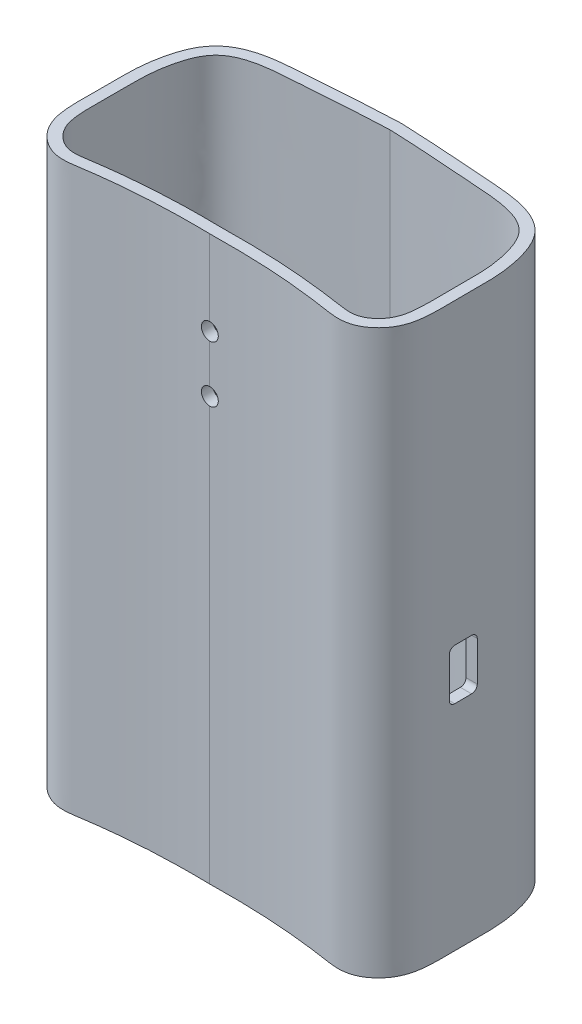
SolidWorks part; units mm, degrees
ref_plane "Ön Düzlem" through (0, 0, 0) normal (0, 0, 1) x (1, 0, 0)
ref_plane "Üst Düzlem" through (0, 0, 0) normal (0, 1, 0) x (1, 0, 0)
ref_plane "Sağ Düzlem" through (0, 0, 0) normal (1, 0, 0) x (0, 0, -1)
sketch "Çizim1" plane through (0, 0, 0) normal (0, 1, 0) x (1, 0, 0)
  line L0 (0, 17.9288) -> (0, -12.0712) construction
  line L1 (0, 0) -> (-30, 0) construction
  line L2 (-108.3091, -42.1463) -> (-63.9653, -42.1463) construction
  spline S0 degree 3 poles (0, 17.9288) (-5.8202, 17.7095) (-13.9034, 17.0426) (-26.8757, 16.196) (-29.5503, 8.9293) (-30.0905, 4.3361) (-29.9407, -0.8874) (-30.1549, -5.7017) (-29.6372, -10.9288) (-26.0312, -14.0818) (-15.7201, -12.3493) (-7.8072, -11.9389) (0, -12.0712) knots 0 0 0 0 0.19846 0.336013 0.394477 0.45973 0.505377 0.582751 0.635933 0.690009 0.731881 1 1 1 1
  spline S1 degree 3 poles (0, 17.9288) (5.8202, 17.7095) (13.9034, 17.0426) (26.8757, 16.196) (29.5503, 8.9293) (30.0905, 4.3361) (29.9407, -0.8874) (30.1549, -5.7017) (29.6372, -10.9288) (26.0312, -14.0818) (15.7201, -12.3493) (7.8072, -11.9389) (0, -12.0712) knots 0 0 0 0 0.19846 0.336013 0.394477 0.45973 0.505377 0.582751 0.635933 0.690009 0.731881 1 1 1 1
  spline S2 degree 1 poles (0, 19.9303) (0, -14.0714) knots 0 0 1 1 construction
  spline S3 degree 1 poles (0, 19.9303) (0, -14.0714) knots 0 0 1 1 construction
  spline S4 degree 3 poles (0, 19.9303) (-0.4569, 19.913) (-1.3788, 19.8761) (-3.1568, 19.7944) (-5.3169, 19.678) (-7.8418, 19.5195) (-11.19, 19.2895) (-14.5919, 19.03) (-18.2872, 18.7842) (-21.2619, 18.4861) (-24.2247, 17.8563) (-26.5803, 16.8232) (-28.2551, 15.5188) (-29.6889, 13.8306) (-30.7777, 11.4296) (-31.5143, 8.5883) (-31.9232, 5.825) (-32.0441, 3.0566) (-31.9879, 0.4286) (-32.0171, -2.0683) (-32.052, -4.7106) (-32.0036, -7.4061) (-31.6486, -10.0115) (-30.6275, -12.1561) (-29.5067, -13.557) (-28.1065, -14.6986) (-26.705, -15.3667) (-25.4582, -15.6359) (-24.2895, -15.7185) (-22.9553, -15.6032) (-21.6185, -15.3841) (-20.348, -15.2005) (-19.0747, -15.0274) (-17.3942, -14.8187) (-15.3102, -14.5944) (-12.8229, -14.3819) (-9.5026, -14.1699) (-6.1385, -14.0592) (-2.6849, -14.0381) (-0.8891, -14.0564) (0, -14.0714) knots -0.000856 -0.000856 -0.000856 -0.000856 0.014788 0.030433 0.061722 0.093011 0.1243 0.186877 0.218166 0.249455 0.280744 0.312033 0.327677 0.343322 0.37461 0.405899 0.437188 0.468477 0.499766 0.531055 0.562344 0.593633 0.624921 0.640566 0.65621 0.671855 0.687499 0.695321 0.703144 0.718788 0.734432 0.750077 0.765721 0.781366 0.812655 0.843944 0.875232 0.93781 0.969099 1.000388 1.000388 1.000388 1.000388
  spline S5 degree 3 poles (0, -14.0714) (0.8891, -14.0564) (2.6849, -14.0381) (6.1385, -14.0592) (9.5026, -14.1699) (12.8229, -14.3819) (15.3102, -14.5944) (17.3942, -14.8187) (19.0747, -15.0274) (20.348, -15.2005) (21.6185, -15.3841) (22.9553, -15.6032) (24.2895, -15.7185) (25.4582, -15.6359) (26.705, -15.3667) (28.1065, -14.6986) (29.5067, -13.557) (30.6275, -12.1561) (31.6486, -10.0115) (32.0036, -7.4061) (32.052, -4.7106) (32.0171, -2.0683) (31.9879, 0.4286) (32.0441, 3.0566) (31.9232, 5.825) (31.5143, 8.5883) (30.7777, 11.4296) (29.6889, 13.8306) (28.2551, 15.5188) (26.5803, 16.8232) (24.2247, 17.8563) (21.2619, 18.4861) (18.2872, 18.7842) (14.5919, 19.03) (11.19, 19.2895) (7.8418, 19.5195) (5.3169, 19.678) (3.1568, 19.7944) (1.3788, 19.8761) (0.4569, 19.913) (0, 19.9303) knots -0.000856 -0.000856 -0.000856 -0.000856 0.030433 0.061722 0.1243 0.155588 0.186877 0.218166 0.233811 0.249455 0.265099 0.280744 0.296388 0.304211 0.312033 0.327677 0.343322 0.358966 0.37461 0.405899 0.437188 0.468477 0.499766 0.531055 0.562344 0.593633 0.624921 0.65621 0.671855 0.687499 0.718788 0.750077 0.781366 0.812655 0.875232 0.906521 0.93781 0.969099 0.984743 1.000388 1.000388 1.000388 1.000388
  dimension "D1" = 30
  dimension "D2" = 30
  dimension "D3" = 2
extrude "Yükseklik-Ekstrüzyon1" add sketch "Çizim1" along normal blind 100
sketch "Çizim2" plane through (0, 100, 0) normal (0, 1, 0) x (1, 0, 0)
  line L0 (0, -14.0714) -> (0, -12.0712)
ref_plane "Düzlem1" through (0, 0, 14.0714) normal (0, 0, -1) x (-1, 0, 0)
sketch "Çizim3" plane through (0, 0, 14.0714) normal (0, 0, -1) x (-1, 0, 0)
  line L0 (0, 100) -> (0, 0) construction
  circle A0 centre (0, 85) radius 1.5
  circle A1 centre (0, 75) radius 1.5
  dimension "D1" = 10
  dimension "D3" = 3
  dimension "D2" = 15
extrude "Kes-Ekstrüzyon1" cut sketch "Çizim3" along normal blind 10
sketch "Çizim4" plane through (0, 0, 0) normal (0, -1, 0) x (1, 0, 0)
  spline S5 degree 3 poles (3998.4121, 83.4226) (-102.3546, -17.7812) (-29.2856, -21.2861) (3.1568, -19.7944) (5.3169, -19.678) (7.8418, -19.5195) (11.19, -19.2895) (14.5919, -19.03) (18.2872, -18.7842) (21.2619, -18.4861) (24.2247, -17.8563) (26.5803, -16.8232) (28.2551, -15.5188) (29.6889, -13.8306) (30.7777, -11.4296) (31.5143, -8.5883) (31.9232, -5.825) (32.0441, -3.0566) (31.9879, -0.4286) (32.0171, 2.0683) (32.052, 4.7106) (32.0036, 7.4061) (31.6486, 10.0115) (30.6275, 12.1561) (29.5067, 13.557) (28.1065, 14.6986) (26.705, 15.3667) (25.4582, 15.6359) (24.2895, 15.7185) (22.9553, 15.6032) (21.6185, 15.3841) (20.348, 15.2005) (19.0747, 15.0274) (17.3942, 14.8187) (15.3102, 14.5944) (12.8229, 14.3819) (9.5026, 14.1699) (6.1385, 14.0592) (-43.8501, 13.7536) (-145.9249, 35.9842) (3997.0667, -133.1935) knots -1.08014 -1.08014 -1.08014 -1.08014 0.014788 0.030433 0.061722 0.093011 0.1243 0.186877 0.218166 0.249455 0.280744 0.312033 0.327677 0.343322 0.37461 0.405899 0.437188 0.468477 0.499766 0.531055 0.562344 0.593633 0.624921 0.640566 0.65621 0.671855 0.687499 0.695321 0.703144 0.718788 0.734432 0.750077 0.765721 0.781366 0.812655 0.843944 0.875232 0.93781 0.969099 2.686743 2.686743 2.686743 2.686743 only from (0, -19.9303) to (0, 14.0714)
  spline S6 degree 3 poles (-3996.9772, -133.1899) (145.9234, 35.9838) (43.8498, 13.7536) (-6.1385, 14.0592) (-9.5026, 14.1699) (-12.8229, 14.3819) (-15.3102, 14.5944) (-17.3942, 14.8187) (-19.0747, 15.0274) (-20.348, 15.2005) (-21.6185, 15.3841) (-22.9553, 15.6032) (-24.2895, 15.7185) (-25.4582, 15.6359) (-26.705, 15.3667) (-28.1065, 14.6986) (-29.5067, 13.557) (-30.6275, 12.1561) (-31.6486, 10.0115) (-32.0036, 7.4061) (-32.052, 4.7106) (-32.0171, 2.0683) (-31.9879, -0.4286) (-32.0441, -3.0566) (-31.9232, -5.825) (-31.5143, -8.5883) (-30.7777, -11.4296) (-29.6889, -13.8306) (-28.2551, -15.5188) (-26.5803, -16.8232) (-24.2247, -17.8563) (-21.2619, -18.4861) (-18.2872, -18.7842) (-14.5919, -19.03) (-11.19, -19.2895) (-7.8418, -19.5195) (-5.3169, -19.678) (-3.1568, -19.7944) (29.2854, -21.2861) (102.3539, -17.7813) (-3998.3551, 83.4212) knots -1.687199 -1.687199 -1.687199 -1.687199 0.030433 0.061722 0.1243 0.155588 0.186877 0.218166 0.233811 0.249455 0.265099 0.280744 0.296388 0.304211 0.312033 0.327677 0.343322 0.358966 0.37461 0.405899 0.437188 0.468477 0.499766 0.531055 0.562344 0.593633 0.624921 0.65621 0.671855 0.687499 0.718788 0.750077 0.781366 0.812655 0.875232 0.906521 0.93781 0.969099 0.984743 2.079666 2.079666 2.079666 2.079666 only from (0, 14.0714) to (0, -19.9303)
  spline S7 degree 3 poles (0, -19.9303) (0.4569, -19.913) (1.3788, -19.8761) (3.1568, -19.7944) (5.3169, -19.678) (7.8418, -19.5195) (11.19, -19.2895) (14.5919, -19.03) (18.2872, -18.7842) (21.2619, -18.4861) (24.2247, -17.8563) (26.5803, -16.8232) (28.2551, -15.5188) (29.6889, -13.8306) (30.7777, -11.4296) (31.5143, -8.5883) (31.9232, -5.825) (32.0441, -3.0566) (31.9879, -0.4286) (32.0171, 2.0683) (32.052, 4.7106) (32.0036, 7.4061) (31.6486, 10.0115) (30.6275, 12.1561) (29.5067, 13.557) (28.1065, 14.6986) (26.705, 15.3667) (25.4582, 15.6359) (24.2895, 15.7185) (22.9553, 15.6032) (21.6185, 15.3841) (20.348, 15.2005) (19.0747, 15.0274) (17.3942, 14.8187) (15.3102, 14.5944) (12.8229, 14.3819) (9.5026, 14.1699) (6.1385, 14.0592) (2.6849, 14.0381) (0.8891, 14.0564) (0, 14.0714) knots -0.000856 -0.000856 -0.000856 -0.000856 0.014788 0.030433 0.061722 0.093011 0.1243 0.186877 0.218166 0.249455 0.280744 0.312033 0.327677 0.343322 0.37461 0.405899 0.437188 0.468477 0.499766 0.531055 0.562344 0.593633 0.624921 0.640566 0.65621 0.671855 0.687499 0.695321 0.703144 0.718788 0.734432 0.750077 0.765721 0.781366 0.812655 0.843944 0.875232 0.93781 0.969099 1.000388 1.000388 1.000388 1.000388
  spline S8 degree 3 poles (0, 14.0714) (-0.8891, 14.0564) (-2.6849, 14.0381) (-6.1385, 14.0592) (-9.5026, 14.1699) (-12.8229, 14.3819) (-15.3102, 14.5944) (-17.3942, 14.8187) (-19.0747, 15.0274) (-20.348, 15.2005) (-21.6185, 15.3841) (-22.9553, 15.6032) (-24.2895, 15.7185) (-25.4582, 15.6359) (-26.705, 15.3667) (-28.1065, 14.6986) (-29.5067, 13.557) (-30.6275, 12.1561) (-31.6486, 10.0115) (-32.0036, 7.4061) (-32.052, 4.7106) (-32.0171, 2.0683) (-31.9879, -0.4286) (-32.0441, -3.0566) (-31.9232, -5.825) (-31.5143, -8.5883) (-30.7777, -11.4296) (-29.6889, -13.8306) (-28.2551, -15.5188) (-26.5803, -16.8232) (-24.2247, -17.8563) (-21.2619, -18.4861) (-18.2872, -18.7842) (-14.5919, -19.03) (-11.19, -19.2895) (-7.8418, -19.5195) (-5.3169, -19.678) (-3.1568, -19.7944) (-1.3788, -19.8761) (-0.4569, -19.913) (0, -19.9303) knots -0.000856 -0.000856 -0.000856 -0.000856 0.030433 0.061722 0.1243 0.155588 0.186877 0.218166 0.233811 0.249455 0.265099 0.280744 0.296388 0.304211 0.312033 0.327677 0.343322 0.358966 0.37461 0.405899 0.437188 0.468477 0.499766 0.531055 0.562344 0.593633 0.624921 0.65621 0.671855 0.687499 0.718788 0.750077 0.781366 0.812655 0.875232 0.906521 0.93781 0.969099 0.984743 1.000388 1.000388 1.000388 1.000388
  dimension "D1" = 0
extrude "Yükseklik-Ekstrüzyon2" add sketch "Çizim4" against normal blind 4
ref_plane "Düzlem2" through (0, 73.5, 14.0714) normal (0, -1, 0) x (-1, 0, 0)
sketch "Çizim5" plane through (0, 73.5, 14.0714) normal (0, -1, 0) x (1, 0, 0)
  line L0 (0, -14.0714) -> (-28.4895, -14.0714)
  line L1 (-28.4895, -14.0714) -> (-57.0626, -14.0714)
ref_plane "Düzlem3" through (0, 0, 0) normal (-1, 0, 0) x (0, 0, -1)
sketch "Çizim6" plane through (0, 0, 0) normal (-1, 0, 0) x (0, 0, -1)
  line L0 (19.9303, 0) -> (-15.6852, 0) construction
  line L1 (-2.5714, -47) -> (0.4286, -47)
  line L2 (-3.5714, -46) -> (-3.5714, -39)
  line L3 (-2.5714, -38) -> (0.4286, -38)
  line L4 (1.4286, -46) -> (1.4286, -39)
  arc A0 (0.4286, -38) -> (1.4286, -39) centre (0.4286, -39) cw
  arc A1 (-3.5714, -39) -> (-2.5714, -38) centre (-2.5714, -39) cw
  arc A2 (-2.5714, -47) -> (-3.5714, -46) centre (-2.5714, -46) cw
  arc A3 (0.4286, -47) -> (1.4286, -46) centre (0.4286, -46) ccw
  point P9 (1.4286, -38)
  point P12 (-3.5714, -38)
  point P17 (1.4286, -47)
  dimension "D5" = 1
  dimension "D1" = 38
  dimension "D2" = 9
  dimension "D3" = 5
  dimension "D4" = 10.5
extrude "Kes-Ekstrüzyon2" cut sketch "Çizim6" against normal blind 44
